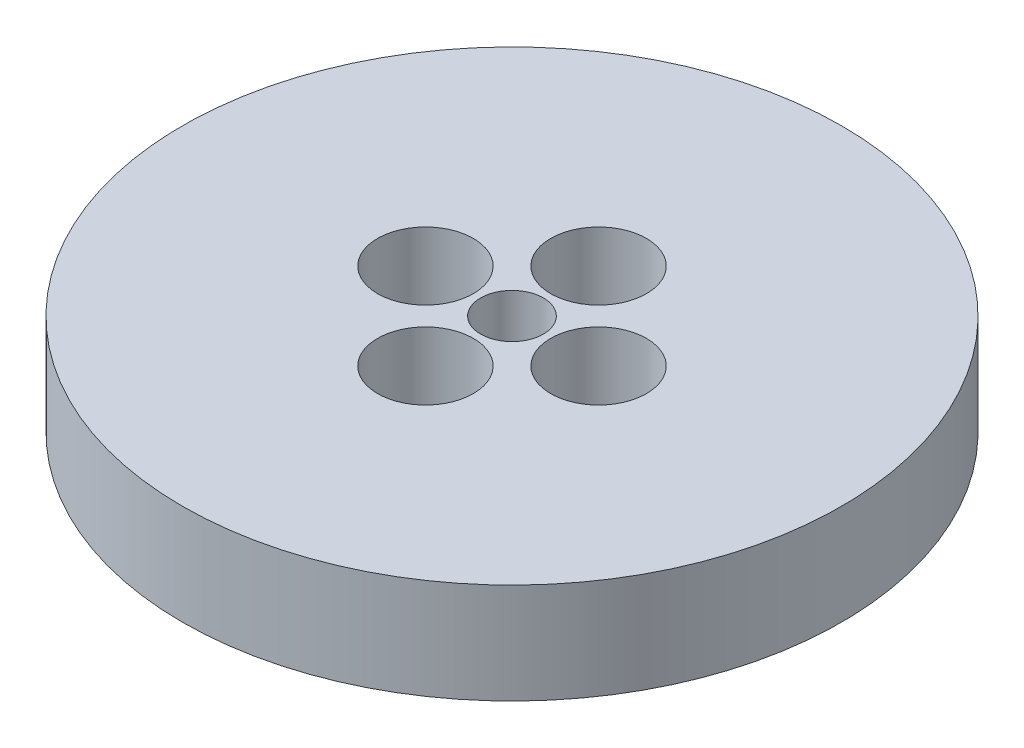
SolidWorks part; units mm, degrees
ref_plane "Front Plane" through (0, 0, 0) normal (0, 0, 1) x (1, 0, 0)
ref_plane "Top Plane" through (0, 0, 0) normal (0, 1, 0) x (1, 0, 0)
ref_plane "Right Plane" through (0, 0, 0) normal (1, 0, 0) x (0, 0, -1)
sketch "Sketch1" plane through (0, 0, 0) normal (0, 1, 0) x (1, 0, 0)
  circle A0 centre (0, 0) radius 52.5
  dimension "FLANGE_OD" = 105
extrude "Boss-Extrude1" add sketch "Sketch1" along normal blind 16
sketch "Sketch2" plane through (0, 0, 0) normal (0, 1, 0) x (1, 0, 0)
  circle A0 centre (0, 0) radius 5
  dimension "BORE_D" = 10
extrude "Cut-Extrude1" cut sketch "Sketch2" along normal through all
sketch "Sketch3" plane through (0, 16, 0) normal (0, 1, 0) x (1, 0, 0)
  circle A0 centre (0, 0) radius 13.7886 construction
  circle A1 centre (-13.7886, 0) radius 7.6289
  dimension "BOLT_D" = 15.2578
  dimension "BOLT_PCD" = 27.5772
extrude "Cut-Extrude2" cut sketch "Sketch3" against normal blind 15.2367
pattern_circular "CirPattern1" count 4 over 360 about axis through (0, 0, 0) along (0, 1, 0) of "Cut-Extrude2"
